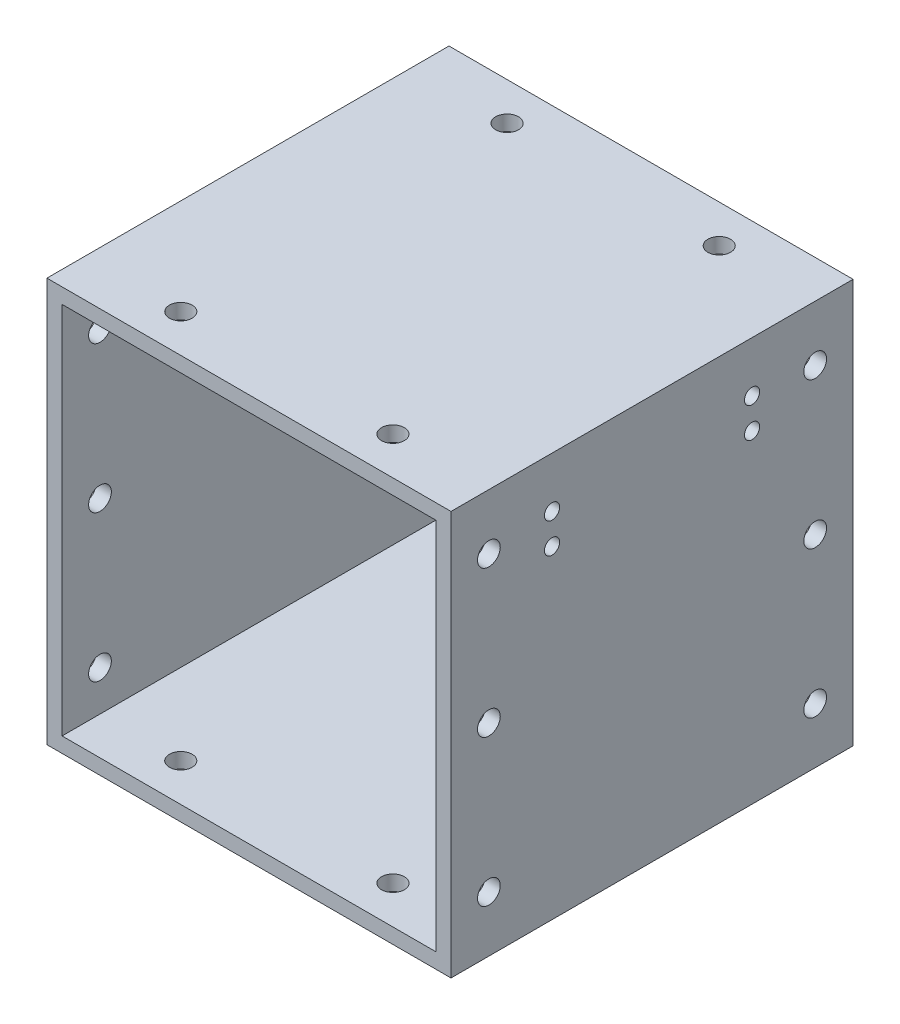
SolidWorks part; units mm, degrees
note: '?' marks a value the reader was unsure of.
material "1.4301 (X5CrNi18-10)"
ref_plane "Front Plane" through (0, 0, 0) normal (0, 0, 1) x (1, 0, 0)
ref_plane "Top Plane" through (0, 0, 0) normal (0, 1, 0) x (1, 0, 0)
ref_plane "Right Plane" through (0, 0, 0) normal (1, 0, 0) x (0, 0, -1)
ref_axis "Axis1" through (0, 0, 23.7877) along (0, 0, 1)?
ref_plane "Plane1" through (0, 0, 57) normal (0, 0, 1) x (1, 0, 0)
ref_axis "Elbow" through (0, -41, 181.6) along (0, 1, 0)?
ref_plane "Plane2" through (0, 0, 181.6) normal (0, 0, 1) x (1, 0, 0)
ref_plane "Plane3" through (0, 0, 136.6) normal (0, 0, 1) x (1, 0, 0)
ref_point "Point2"
sketch "Sketch1" plane through (0, 0, 57) normal (0, 0, 1) x (1, 0, 0)
  line L0 (40, 40) -> (-40, 40) construction
  line L1 (-40, -40) -> (40, -40)
  line L2 (-40, -40) -> (-40, 40)
  line L3 (-40, 40) -> (40, 40)
  line L4 (40, -40) -> (40, 40)
  line L5 (-40, -40) -> (40, 40) construction
  line L6 (-40, 40) -> (40, -40) construction
  line L7 (-37, -37) -> (-37, 37)
  line L8 (-37, 37) -> (37, 37)
  line L9 (37, -37) -> (37, 37)
  line L10 (-37, -37) -> (37, -37)
  line L11 (-40, 40) -> (-40, -40) construction
  point P0 (0, 0)
  dimension "D3" = 3
extrude "Boss-Extrude1" add sketch "Sketch1" along normal up to vertex (79.6 mm away)
hole_wizard "M4 Clearance Hole1" positions "3DSketch3" profile "Sketch4" hole size "M4" standard "DIN" end condition up to next
sketch3d "3DSketch3"
  circle A0 centre (37, 29, 64.5) radius 1.65 construction
  circle A1 centre (37, 0, 64.5) radius 1.65 construction
  circle A2 centre (37, -29, 64.5) radius 1.65 construction
  circle A5 centre (21, 37, 64.5) radius 1.65 construction
  circle A6 centre (-21, 37, 64.5) radius 1.65 construction
  circle A7 centre (-37, 29, 64.5) radius 1.65 construction
  circle A8 centre (-37, 0, 64.5) radius 1.65 construction
  circle A9 centre (-37, -29, 64.5) radius 1.65 construction
  circle A10 centre (-21, -37, 64.5) radius 1.65 construction
  circle A11 centre (21, -37, 64.5) radius 1.65 construction
  circle A12 centre (-21, 37, 129.1) radius 1.65 construction
  circle A13 centre (21, 37, 129.1) radius 1.65 construction
  circle A14 centre (37, 29, 129.1) radius 1.65 construction
  circle A17 centre (37, 0, 129.1) radius 1.65 construction
  circle A18 centre (37, -29, 129.1) radius 1.65 construction
  circle A19 centre (21, -37, 129.1) radius 1.65 construction
  circle A20 centre (-21, -37, 129.1) radius 1.65 construction
  circle A21 centre (-37, -29, 129.1) radius 1.65 construction
  circle A22 centre (-37, 29, 129.1) radius 1.65 construction
  circle A23 centre (-37, 0, 129.1) radius 1.65 construction
  point P0 (40, 29, 64.5)
  point P2 (40, -29, 64.5)
  point P4 (40, 0, 64.5)
  point P9 (38.65, 29, 64.5)
  point P13 (38.65, 0, 64.5)
  point P17 (38.65, -29, 64.5)
  point P18 (21, 40, 64.5)
  point P20 (-21, 40, 64.5)
  point P22 (-40, 29, 64.5)
  point P24 (-40, 0, 64.5)
  point P26 (-40, -29, 64.5)
  point P28 (21, -40, 64.5)
  point P30 (-21, -40, 64.5)
  point P41 (21, 38.65, 64.5)
  point P45 (-21, 38.65, 64.5)
  point P48 (-38.65, 29, 64.5)
  point P52 (-38.65, 0, 64.5)
  point P55 (-38.65, -29, 64.5)
  point P58 (-21, -38.65, 64.5)
  point P62 (21, -38.65, 64.5)
  point P67 (40, 29, 129.1)
  point P69 (40, 0, 129.1)
  point P71 (40, -29, 129.1)
  point P73 (-21, 40, 129.1)
  point P75 (21, 40, 129.1)
  point P81 (-40, -29, 129.1)
  point P83 (-21, -40, 129.1)
  point P85 (21, -40, 129.1)
  point P90 (-21, 38.65, 129.1)
  point P94 (21, 38.65, 129.1)
  point P98 (38.65, 29, 129.1)
  point P108 (38.65, 0, 129.1)
  point P112 (38.65, -29, 129.1)
  point P115 (21, -38.65, 129.1)
  point P118 (-21, -38.65, 129.1)
  point P122 (-38.65, -29, 129.1)
  point P125 (-40, 0, 129.1)
  point P127 (-40, 29, 129.1)
  point P132 (-38.65, 29, 129.1)
  point P136 (-38.65, 0, 129.1)
sketch "Sketch4" plane through (40, 29, 64.5) normal (0, 1, 0) x (0, 0, -1)
  line L0 (0, 0) -> (0, 3)
  line L1 (0, 3) -> (2.25, 3)
  line L2 (2.25, 3) -> (2.25, 0)
  line L5 (2.25, 0) -> (0, 0)
  line L11 (0, -6.35) -> (0, 107.95) construction
  dimension "Thru Hole Dia." = 4.5
  dimension "Thru Hole Depth" = 3
sketch "Sketch7" plane through (40, 0, 0) normal (1, 0, 0) x (0, 0, -1)
  line L0 (-136.6, 37) -> (-57, 37) construction
  line L1 (-136.6, 37) -> (-57, 37) construction
  line L2 (-136.6, 27) -> (-57, 27) construction
  line L3 (-116.6, 30) -> (-116.6, 24) construction
  line L5 (-96.8, 27) -> (-96.8, 37) construction
  point P14 (-116.6, 27)
  point P15 (-116.6, 24)
  point P17 (-116.6, 30)
  point P23 (-77, 24)
  point P24 (-77, 30)
  dimension "D1" = 10
  dimension "D2" = 20
  dimension "D3" = 6
hole_wizard "Ø3.0 (3) Diameter Hole1" positions "Sketch7" profile "Sketch6" hole size "Ø3.0" standard "DIN"
sketch "Sketch6" plane through (40, 30, 77) normal (0, 1, 0) x (0, 0, -1)
  line L0 (0, 0) -> (0, 3)
  line L1 (0, 3) -> (1.5, 3)
  line L2 (1.5, 3) -> (1.5, 0)
  line L5 (1.5, 0) -> (0, 0)
  line L11 (0, -6.35) -> (0, 107.95) construction
  dimension "Thru Hole Dia." = 3
  dimension "Thru Hole Depth" = 3
